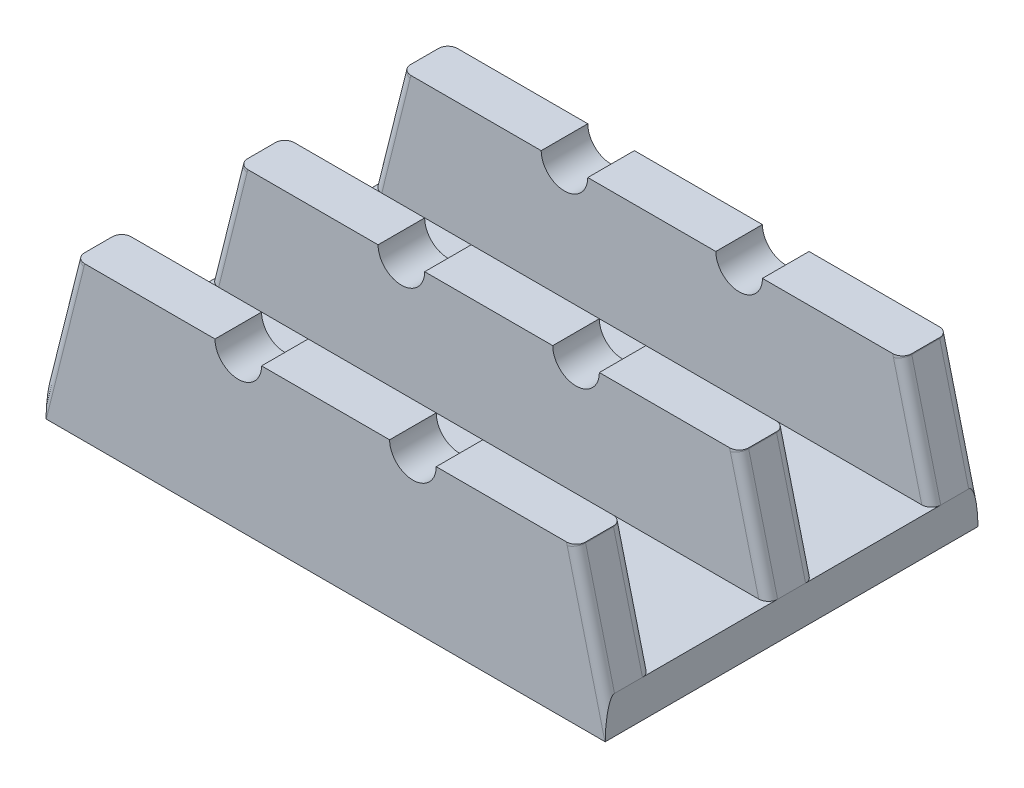
SolidWorks part; units mm, degrees
ref_plane "Front Plane" through (0, 0, 0) normal (0, 0, 1) x (1, 0, 0)
ref_plane "Top Plane" through (0, 0, 0) normal (0, 1, 0) x (1, 0, 0)
ref_plane "Right Plane" through (0, 0, 0) normal (1, 0, 0) x (0, 0, -1)
sketch "Sketch1" plane through (0, 0, 0) normal (0, 1, 0) x (1, 0, 0)
  line L1 (-9.75, -14.75) -> (9.75, -14.75)
  line L2 (-9.75, -14.75) -> (-9.75, 14.75)
  line L3 (-9.75, 14.75) -> (9.75, 14.75)
  line L4 (9.75, -14.75) -> (9.75, 14.75)
  line L5 (-9.75, -14.75) -> (9.75, 14.75) construction
  line L6 (-9.75, 14.75) -> (9.75, -14.75) construction
  point P0 (0, 0)
  dimension "D1" = 19.5
  dimension "D2" = 29.5
extrude "Boss-Extrude1" add sketch "Sketch1" along normal blind 4 contours L2 L1 L4 L3
sketch "Sketch2" plane through (0, 4, 0) normal (0, 1, 0) x (1, 0, 0)
  line L1 (-30, -20) -> (30, -20)
  line L2 (-30, -20) -> (-30, 20)
  line L3 (-30, 20) -> (30, 20)
  line L4 (30, -20) -> (30, 20)
  line L5 (-30, -20) -> (30, 20) construction
  line L6 (-30, 20) -> (30, -20) construction
  point P0 (0, 0)
  dimension "D1" = 60
  dimension "D2" = 40
extrude "Boss-Extrude3" add sketch "Sketch2" along normal blind 4
sketch "Sketch3" plane through (0, 8, 0) normal (0, 1, 0) x (1, 0, 0)
  line L0 (30, -20) -> (30, 20) construction
  line L1 (-30, 20) -> (30, 20)
  line L2 (-30, 20) -> (-30, 15)
  line L3 (-30, 15) -> (30, 15)
  line L4 (30, 20) -> (30, 15)
  line L6 (30, -20) -> (30, -15)
  line L7 (-30, -15) -> (30, -15)
  line L8 (-30, -20) -> (-30, -15)
  line L9 (-30, -20) -> (30, -20)
  line M9 (30, -20) -> (30, 20)
  line M10 (30, 20) -> (-30, 20)
  line M11 (-30, 20) -> (-30, -20)
  dimension "D1" = 5
extrude "Boss-Extrude4" add sketch "Sketch3" along normal blind 20 contours L3 M11 M9 M10 | L6 L7 L8 L9 region at (0, 8, -17.5)
chamfer "Chamfer1" distance 5 distance2 20 1 edges at (-30, 28, 17.5) first distance on face at (0, 28, 17.5)
chamfer "Chamfer2" distance 20 distance2 5 1 edges at (-30, 28, -17.5) first distance on face at (-30, 12.5714, -2.1429)
chamfer "Chamfer3" distance 20 distance2 5 2 edges at (30, 28, -17.5) (30, 28, 17.5) first distance on face at (30, 17, 0)
fillet "Fillet1" radius 10 4 edges at (25, 28, 17.5) (25, 28, -17.5) (-25, 28, 17.5) (-25, 28, -17.5)
fillet "Fillet2" radius 1 10 edges at (28.4468, 14.2127, -20) (23.3464, 25.8821, -20) (-28.4468, 14.2127, -20) (-23.3464, 25.8821, -20) (-28.4468, 14.2127, 20) (-23.3464, 25.8821, 20) (28.4468, 14.2127, 20) (23.3464, 25.8821, 20) (0, 28, -20) (0, 28, 20)
sketch "Sketch4" plane through (0, 8, 0) normal (0, 1, 0) x (1, 0, 0)
  line L0 (30, -15) -> (30, 15) construction
  line L1 (-30, 2.5) -> (30, 2.5)
  line L2 (-30, 2.5) -> (-30, -2.5)
  line L3 (-30, -2.5) -> (30, -2.5)
  line L4 (30, 2.5) -> (30, -2.5)
  line L5 (-30, 2.5) -> (30, -2.5) construction
  line L6 (-30, -2.5) -> (30, 2.5) construction
  point P0 (0, 0)
  dimension "D1" = 5
extrude "Boss-Extrude5" add sketch "Sketch4" along normal blind 20
chamfer "Chamfer4" distance 20 distance2 5 2 edges at (30, 28, 0) (-30, 28, 0) first distance on face at (30, 11.3671, 0) first distance on face at (-30, 11.3671, 0)
fillet "Fillet3" radius 10 2 edges at (-25, 28, 0) (25, 28, 0)
fillet "Fillet4" radius 1 10 edges at (28.4468, 14.2127, -2.5) (23.3464, 25.8821, -2.5) (-28.4468, 14.2127, -2.5) (-23.3464, 25.8821, -2.5) (-28.4468, 14.2127, 2.5) (-23.3464, 25.8821, 2.5) (28.4468, 14.2127, 2.5) (23.3464, 25.8821, 2.5) (0, 28, -2.5) (0, 28, 2.5)
fillet "Fillet5" radius 1 10 edges at (-28.4468, 14.2127, 15) (-23.3464, 25.8821, 15) (28.4468, 14.2127, 15) (23.3464, 25.8821, 15) (-28.4468, 14.2127, -15) (-23.3464, 25.8821, -15) (28.4468, 14.2127, -15) (23.3464, 25.8821, -15) (0, 28, 15) (0, 28, -15)
sketch "Sketch5" plane through (0, 0, 20) normal (0, 0, 1) x (1, 0, 0)
  line L0 (17.1922, 27) -> (-17.1922, 27) construction
  circle A0 centre (-9.3692, 20.5) radius 2.5
  circle A1 centre (9.3692, 20.5) radius 2.5
  dimension "D1" = 6.5
  dimension "D2" = 20.6
extrude "Cut-Extrude1" cut sketch "Sketch5" against normal through all contours A0 | A1
ref_plane "Plane1" through (0, 28, 0) normal (0, 1, 0) x (1, 0, 0)
sketch "Sketch6" plane through (0, 28, 0) normal (0, 1, 0) x (1, 0, 0)
  line L1 (-35.685, 22.7735) -> (35.685, 22.7735)
  line L2 (-35.685, 22.7735) -> (-35.685, -22.7735)
  line L3 (-35.685, -22.7735) -> (35.685, -22.7735)
  line L4 (35.685, 22.7735) -> (35.685, -22.7735)
  line L5 (-35.685, 22.7735) -> (35.685, -22.7735) construction
  line L6 (-35.685, -22.7735) -> (35.685, 22.7735) construction
  point P0 (0, 0)
extrude "Cut-Extrude2" cut sketch "Sketch6" against normal blind 7.5
